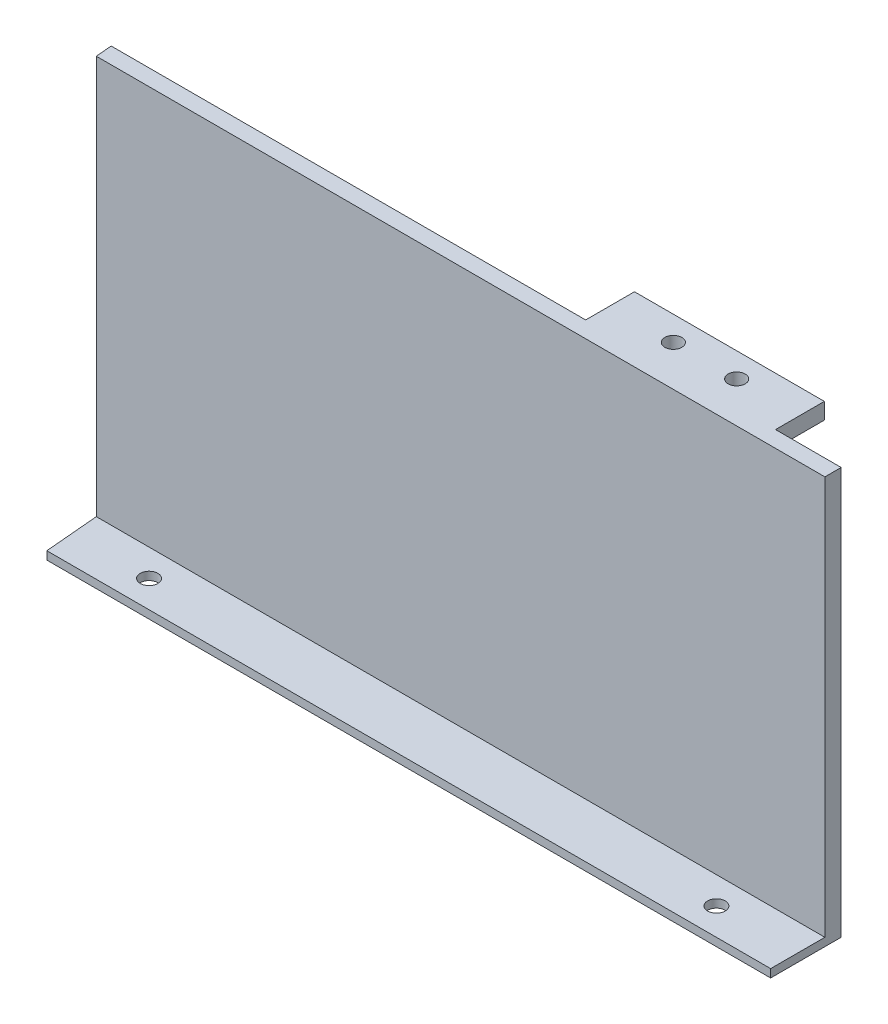
SolidWorks part; units mm, degrees
ref_plane "Front Plane" through (0, 0, 0) normal (0, 0, 1) x (1, 0, 0)
ref_plane "Top Plane" through (0, 0, 0) normal (0, 1, 0) x (1, 0, 0)
ref_plane "Right Plane" through (0, 0, 0) normal (1, 0, 0) x (0, 0, -1)
sketch "Sketch1" plane through (0, 0, 0) normal (0, 1, 0) x (1, 0, 0)
  line L1 (0, 0) -> (134.58, 0)
  line L2 (0, 0) -> (0, 3)
  line L3 (0, 3) -> (134.58, 3)
  line L4 (134.58, 0) -> (134.58, 3)
  dimension "D1" = 3
  dimension "D2" = 134.58
extrude "Boss-Extrude1" add sketch "Sketch1" along normal blind 75
sketch "Sketch2" plane through (0, 0, -3) normal (0, 0, -1) x (-1, 0, 0)
  line L0 (-134.58, 75) -> (0, 75) construction
  line L1 (-122.48, 75) -> (-87.48, 75)
  line L2 (-122.48, 75) -> (-122.48, 72)
  line L3 (-122.48, 72) -> (-87.48, 72)
  line L4 (-87.48, 75) -> (-87.48, 72)
  line L5 (-134.58, 75) -> (-134.58, 0) construction
  dimension "D1" = 12.1
  dimension "D2" = 3
  dimension "D3" = 35
extrude "Boss-Extrude2" add sketch "Sketch2" along normal blind 9
sketch "Sketch3" plane through (0, 75, 0) normal (0, 1, 0) x (1, 0, 0)
  line L0 (87.48, 12) -> (122.48, 12) construction
  line L1 (87.48, 12) -> (87.48, 3) construction
  line L3 (122.48, 12) -> (122.48, 3) construction
  circle A0 centre (110.8133, 7.5) radius 1.575
  circle A1 centre (99.1467, 7.5) radius 1.575
  dimension "D1" = 3.15
  dimension "D2" = 3.15
  dimension "D3" = 4.5
  dimension "D4" = 4.5
  dimension "D5" = 11.6667
  dimension "D6" = 11.6667
extrude "Cut-Extrude1" cut sketch "Sketch3" against normal through all
sketch "Sketch4" plane through (0, 0, 0) normal (0, 0, 1) x (1, 0, 0)
  line L1 (134.58, 75) -> (134.58, 0) construction
  line L3 (0, 0) -> (134.58, 0)
  line L4 (0, 0) -> (0, 1.5)
  line L5 (0, 1.5) -> (134.58, 1.5)
  line L6 (134.58, 0) -> (134.58, 1.5)
  dimension "D1" = 1.5
extrude "Boss-Extrude3" add sketch "Sketch4" along normal blind 10
sketch "Sketch5" plane through (0, 0, 0) normal (0, -1, 0) x (1, 0, 0)
  line L0 (134.58, 10) -> (134.58, -3) construction
  line L1 (0, -3) -> (0, 10) construction
  line L2 (0, 10) -> (134.58, 10) construction
  line L3 (0, 10) -> (1.16, 10)
  line L4 (0, 10) -> (0, -3)
  line L5 (0, -3) -> (0.02, -3)
  line L6 (134.58, -3) -> (0, -3) construction
  line L7 (0.02, -3) -> (1.16, 10)
  circle A0 centre (15, 5) radius 1.625
  circle A1 centre (119.58, 5) radius 1.625
  dimension "D1" = 3.25
  dimension "D2" = 3.25
  dimension "D3" = 15
  dimension "D4" = 15
  dimension "D5" = 5
  dimension "D6" = 5
  dimension "D7" = 1.16
  dimension "D8" = 0.02
extrude "Cut-Extrude2" cut sketch "Sketch5" against normal through all
